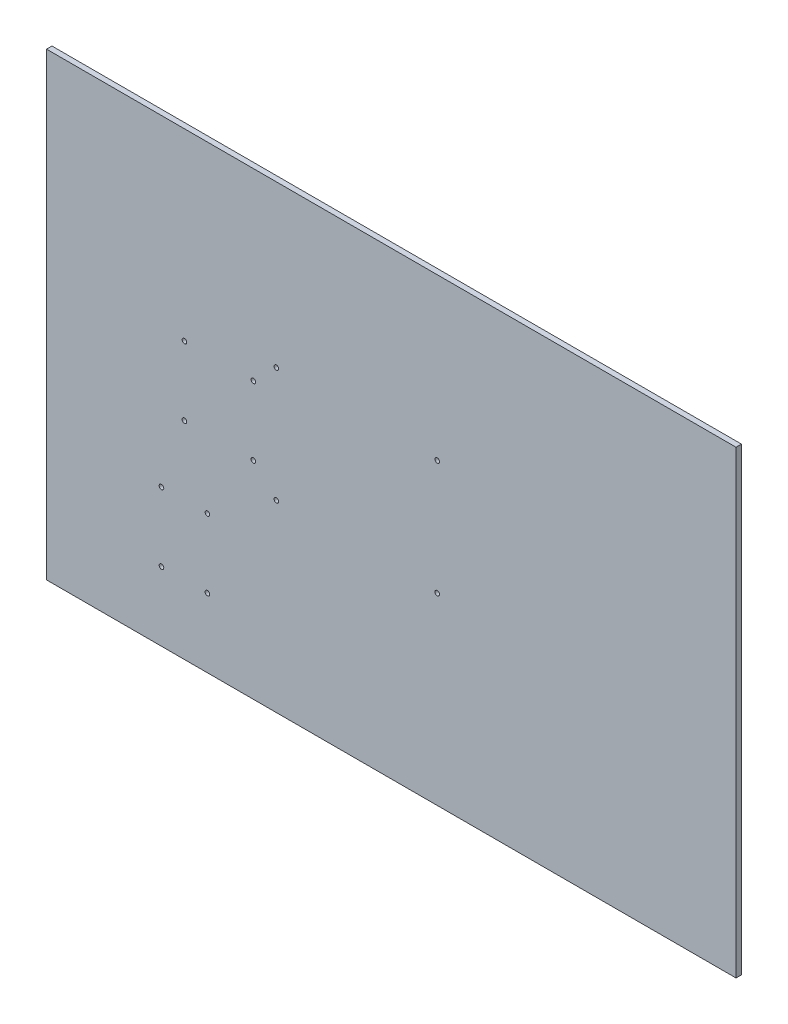
SolidWorks part; units mm, degrees
ref_plane "Front Plane" through (0, 0, 0) normal (0, 0, 1) x (1, 0, 0)
ref_plane "Top Plane" through (0, 0, 0) normal (0, 1, 0) x (1, 0, 0)
ref_plane "Right Plane" through (0, 0, 0) normal (1, 0, 0) x (0, 0, -1)
sketch "Sketch2" plane through (0, 0, 0) normal (0, 0, 1) x (1, 0, 0)
  line L0 (0, 254) -> (0, -254) construction
  line L1 (-381, -254) -> (381, -254)
  line L2 (-381, -254) -> (-381, 254)
  line L3 (-381, 254) -> (381, 254)
  line L4 (381, -254) -> (381, 254)
  line L5 (-381, -254) -> (381, 254) construction
  line L6 (-381, 254) -> (381, -254) construction
  line L7 (-304.8, 254) -> (-304.8, -254) construction
  line L8 (-355.6, 254) -> (-355.6, -254) construction
  line L9 (-330.2, 254) -> (-330.2, -254) construction
  line L10 (-279.4, 254) -> (-279.4, -254) construction
  line L11 (-254, 254) -> (-254, -254) construction
  line L12 (-228.6, 254) -> (-228.6, -254) construction
  line L13 (-203.2, 254) -> (-203.2, -254) construction
  line L14 (-177.8, 254) -> (-177.8, -254) construction
  line L15 (-152.4, 254) -> (-152.4, -254) construction
  line L16 (-127, 254) -> (-127, -254) construction
  line L17 (-101.6, 254) -> (-101.6, -254) construction
  line L18 (-76.2, 254) -> (-76.2, -254) construction
  line L19 (-50.8, 254) -> (-50.8, -254) construction
  line L20 (-25.4, 254) -> (-25.4, -254) construction
  line L21 (25.4, 254) -> (25.4, -254) construction
  line L22 (50.8, 254) -> (50.8, -254) construction
  line L23 (76.2, 254) -> (76.2, -254) construction
  line L24 (101.6, 254) -> (101.6, -254) construction
  line L25 (127, 254) -> (127, -254) construction
  line L26 (152.4, 254) -> (152.4, -254) construction
  line L27 (177.8, 254) -> (177.8, -254) construction
  line L28 (203.2, 254) -> (203.2, -254) construction
  line L29 (228.6, 254) -> (228.6, -254) construction
  line L30 (254, 254) -> (254, -254) construction
  line L31 (279.4, 254) -> (279.4, -254) construction
  line L32 (304.8, 254) -> (304.8, -254) construction
  line L33 (330.2, 254) -> (330.2, -254) construction
  line L34 (355.6, 254) -> (355.6, -254) construction
  line L35 (-381, 0) -> (381, 0) construction
  line L36 (-381, 152.4) -> (381, 152.4) construction
  line L37 (-381, 177.8) -> (381, 177.8) construction
  line L38 (-381, 203.2) -> (381, 203.2) construction
  line L39 (-381, 228.6) -> (381, 228.6) construction
  line L40 (-381, 127) -> (381, 127) construction
  line L41 (-381, 101.6) -> (381, 101.6) construction
  line L42 (-381, 76.2) -> (381, 76.2) construction
  line L43 (-381, 50.8) -> (381, 50.8) construction
  line L44 (-381, 25.4) -> (381, 25.4) construction
  line L45 (-381, -25.4) -> (381, -25.4) construction
  line L46 (-381, -50.8) -> (381, -50.8) construction
  line L47 (-381, -76.2) -> (381, -76.2) construction
  line L48 (-381, -101.6) -> (381, -101.6) construction
  line L49 (-381, -127) -> (381, -127) construction
  line L50 (-381, -152.4) -> (381, -152.4) construction
  line L51 (-381, -177.8) -> (381, -177.8) construction
  line L52 (-381, -203.2) -> (381, -203.2) construction
  line L53 (-381, -228.6) -> (381, -228.6) construction
  line L54 (-381, 12.7) -> (381, 12.7) construction
  circle A0 centre (-228.6, 50.8) radius 2.555
  circle A1 centre (-228.6, -25.4) radius 2.555
  circle A2 centre (-152.4, 50.8) radius 2.555
  circle A3 centre (-152.4, -25.4) radius 2.555
  circle A5 centre (-127, 76.2) radius 2.555
  circle A6 centre (-127, -50.8) radius 2.555
  circle A9 centre (50.8, 76.2) radius 2.555
  circle A10 centre (50.8, -50.8) radius 2.555
  circle A11 centre (-254, -177.8) radius 2.555
  circle A12 centre (-203.2, -177.8) radius 2.555
  circle A13 centre (-254, -101.6) radius 2.555
  circle A14 centre (-203.2, -101.6) radius 2.555
  point P0 (0, 0)
  point P128 (-254, -152.4)
  point P129 (-254, -76.2)
  point P130 (-254, -152.4)
  point P131 (-203.2, -152.4)
  point P132 (-204.8884, -75.0211)
  point P133 (-203.2, -76.2)
  point P134 (-254, -152.4)
  point P135 (-254, -152.4)
  point P136 (0, 0)
  point P137 (-254, -177.8)
  point P138 (-203.2, -177.8)
  point P139 (-254, -76.2)
  point P140 (-254, -101.6)
  point P141 (-203.2, -101.6)
  dimension "D17" = 5.11
  dimension "D18" = 5.11
  dimension "D19" = 5.11
  dimension "D20" = 5.11
  dimension "D22" = 5.11
  dimension "D23" = 5.11
  dimension "D24" = 5.11
  dimension "D25" = 5.11
  dimension "D26" = 5.11
  dimension "D27" = 5.11
  dimension "D28" = 5.11
  dimension "D29" = 5.11
  dimension "D1" = 762
  dimension "D2" = 508
  dimension "D3" = 25.4
  dimension "D4" = 25.4
  dimension "D5" = 25.4
  dimension "D6" = 25.4
  dimension "D7" = 25.4
  dimension "D8" = 25.4
  dimension "D9" = 25.4
  dimension "D10" = 25.4
  dimension "D11" = 25.4
  dimension "D12" = 25.4
  dimension "D13" = 25.4
  dimension "D14" = 25.4
  dimension "D15" = 25.4
  dimension "D16" = 25.4
  dimension "D21" = 12.7
extrude "Boss-Extrude1" add sketch "Sketch2" along normal blind 6
